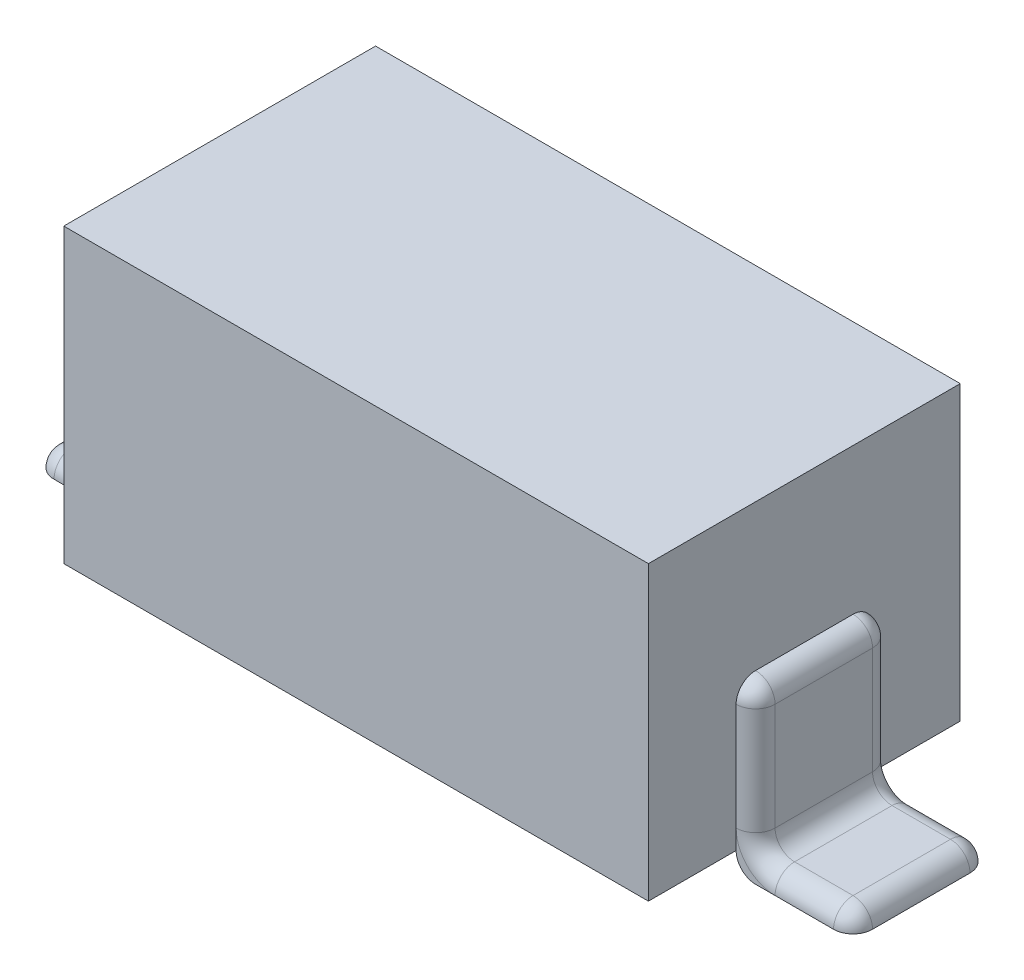
SolidWorks part; units mm, degrees
ref_plane "Front Plane" through (0, 0, 0) normal (0, 0, 1) x (1, 0, 0)
ref_plane "Top Plane" through (0, 0, 0) normal (0, 1, 0) x (1, 0, 0)
ref_plane "Right Plane" through (0, 0, 0) normal (1, 0, 0) x (0, 0, -1)
sketch "Sketch1" plane through (0, 0, 0) normal (0, 1, 0) x (1, 0, 0)
  line L1 (-1.5, -0.8) -> (1.5, -0.8)
  line L2 (-1.5, -0.8) -> (-1.5, 0.8)
  line L3 (-1.5, 0.8) -> (1.5, 0.8)
  line L4 (1.5, -0.8) -> (1.5, 0.8)
  line L5 (-1.5, -0.8) -> (1.5, 0.8) construction
  line L6 (-1.5, 0.8) -> (1.5, -0.8) construction
  point P0 (0, 0)
  dimension "D1" = 1.6
  dimension "D2" = 3
extrude "Boss-Extrude1" add sketch "Sketch1" along normal mid plane 1.5
sketch "Sketch2" plane through (1.5, 0, 0) normal (1, 0, 0) x (0, 0, -1)
  line L1 (-0.35, -0.85) -> (0.35, -0.85)
  line L2 (-0.35, -0.85) -> (-0.35, 0)
  line L3 (-0.35, 0) -> (0.35, 0)
  line L4 (0.35, -0.85) -> (0.35, 0)
  line L5 (-0.35, -0.85) -> (0.35, 0) construction
  line L6 (-0.35, 0) -> (0.35, -0.85) construction
  point P0 (0, -0.425)
  dimension "D1" = 0.85
  dimension "D2" = 0.7
extrude "Boss-Extrude2" add sketch "Sketch2" along normal blind 0.1
sketch "Sketch5" plane through (1.6, 0, 0) normal (1, 0, 0) x (0, 0, -1)
  line L0 (0.35, -0.85) -> (0.35, 0) construction
  line L1 (-0.35, -0.85) -> (0.35, -0.85)
  line L2 (-0.35, -0.85) -> (-0.35, -0.75)
  line L3 (-0.35, -0.75) -> (0.35, -0.75)
  line L4 (0.35, -0.85) -> (0.35, -0.75)
extrude "Boss-Extrude4" add sketch "Sketch5" along normal blind 0.5
fillet "Fillet4" radius 0.1 8 edges at (2.1, -0.75, 0) (1.6, 0, 0) (1.5, -0.85, 0)
mirror "Mirror1" about plane through (0, 0, 0) normal (1, 0, 0) of "Fillet4", "Boss-Extrude2", "Boss-Extrude4"
